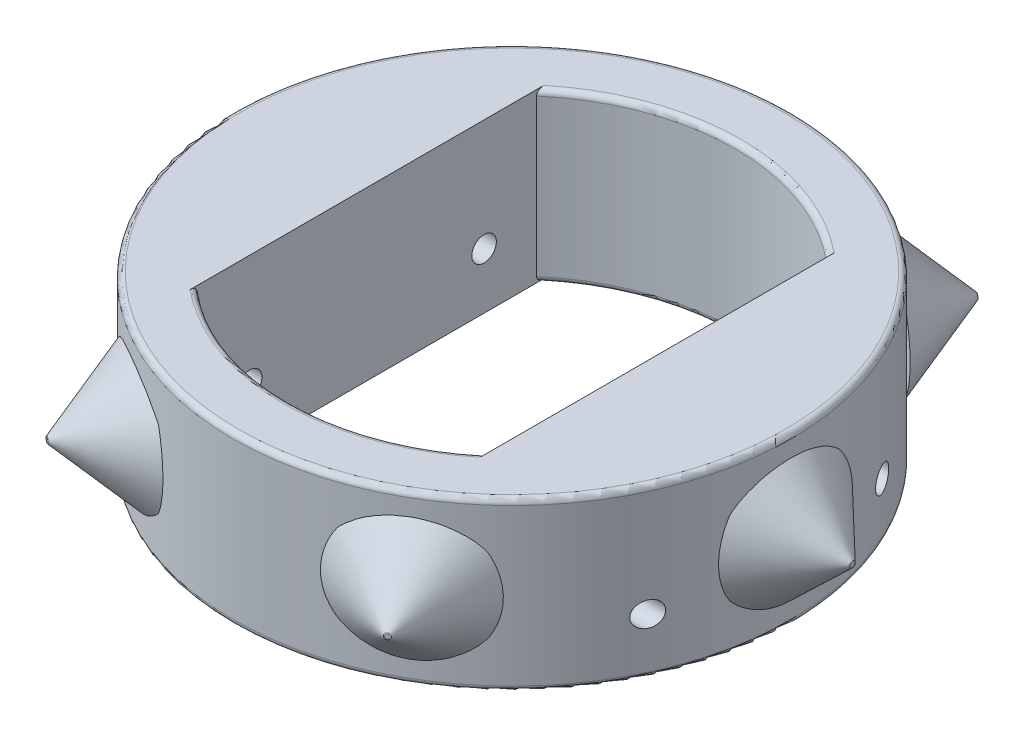
SolidWorks part; units mm, degrees
material "ABS"
ref_plane "正面" through (0, 0, 0) normal (0, 0, 1) x (1, 0, 0)
ref_plane "平面" through (0, 0, 0) normal (0, 1, 0) x (1, 0, 0)
ref_plane "右側面" through (0, 0, 0) normal (1, 0, 0) x (0, 0, -1)
sketch "ｽｹｯﾁ1" plane through (0, 0, 0) normal (0, 1, 0) x (1, 0, 0)
  circle A0 centre (0, 0) radius 25
  circle A1 centre (0, 0) radius 20
  dimension "D1" = 40
  dimension "D2" = 50
extrude "ﾎﾞｽ - 押し出し1" add sketch "ｽｹｯﾁ1" along normal blind 7.5 and the other way blind 7.5
fillet "ﾌｨﾚｯﾄ1" radius 0.5 4 edges at (0, -7.5, 20) (0, -7.5, 25) (0, 7.5, 20) (0, 7.5, 25)
sketch "ｽｹｯﾁ2" plane through (0, 0, 0) normal (0, 0, 1) x (1, 0, 0)
  line L0 (30.4692, 0.2795) -> (24.5, 6)
  line L1 (24.5, 6) -> (24.5, 0)
  line L2 (24.5, 0) -> (30.5, 0) construction
  line L4 (-25, 7) -> (25, 7) construction
  line L5 (-25, 7) -> (25, 7) construction
  line L6 (30.5, 0) -> (24.5, 0)
  line L7 (30.5, 0) -> (30.5, 0.2073)
  arc A0 (30.5, 0.2073) -> (30.4692, 0.2795) centre (30.4, 0.2073) ccw
  point P4 (30.5, 0.25)
  dimension "D5" = 0.1
  dimension "D1" = 0.5
  dimension "D2" = 6
  dimension "D3" = 6
  dimension "D4" = 0.25
revolve "回転1" add sketch "ｽｹｯﾁ2" angle 360 about L6 region at (26.58, 2.0034, 0)
ref_axis "軸1" through (0, -7, 0) along (0, 1, 0)
pattern_circular "円形ﾊﾟﾀｰﾝ5" count 6 over 360 about axis through (0, -7, 0) along (0, 1, 0) of bodies 102
sketch "ｽｹｯﾁ3" plane through (-12.25, 0, 21.2176) normal (0.5, 0, -0.866) x (-0.866, 0, -0.5)
  circle A0 centre (0, 0) radius 4.25
  dimension "D1" = 8.5
extrude "ｶｯﾄ - 押し出し1" cut sketch "ｽｹｯﾁ3" against normal blind 10
pattern_circular "円形ﾊﾟﾀｰﾝ6" count 6 over 360 about axis through (0, -7, 0) along (0, 1, 0) of "ｶｯﾄ - 押し出し1"
sketch "ｽｹｯﾁ4" plane through (0, -7.5, 0) normal (0, -1, 0) x (1, 0, 0)
  line L0 (-13, 15.8509) -> (-13, -15.8509)
  line L1 (13, 15.8509) -> (13, -15.8509)
  circle A0 centre (0, 0) radius 20.5 construction
  arc A1 (-13, 15.8509) -> (-13, -15.8509) centre (0, 0) ccw
  arc A2 (13, -15.8509) -> (13, 15.8509) centre (0, 0) ccw
  point P7 (15.6388, 13.2784)
  dimension "D1" = 13
  dimension "D2" = 13
extrude "ﾎﾞｽ - 押し出し2" add sketch "ｽｹｯﾁ4" against normal up to surface (15 mm away) up to face at (0, 7.5, 20.5)
sketch "ｽｹｯﾁ5" plane through (13, 0, 0) normal (-1, 0, 0) x (0, 0, 1)
  line L0 (15.1987, -2.5) -> (-15.1987, -2.5) construction
  line L3 (0, -8.25) -> (0, 8.25) construction
  line L4 (15.8509, -7.5) -> (-15.8509, -7.5) construction
  circle A0 centre (10.5, -2.5) radius 1.1
  circle A1 centre (-10.5, -2.5) radius 1.1
  point P2 (0, 0)
  dimension "D1" = 2.2
  dimension "D2" = 10.5
  dimension "D3" = 10.5
  dimension "D4" = 5
extrude "ｶｯﾄ - 押し出し2" cut sketch "ｽｹｯﾁ5" against normal through all both and the other way through all
